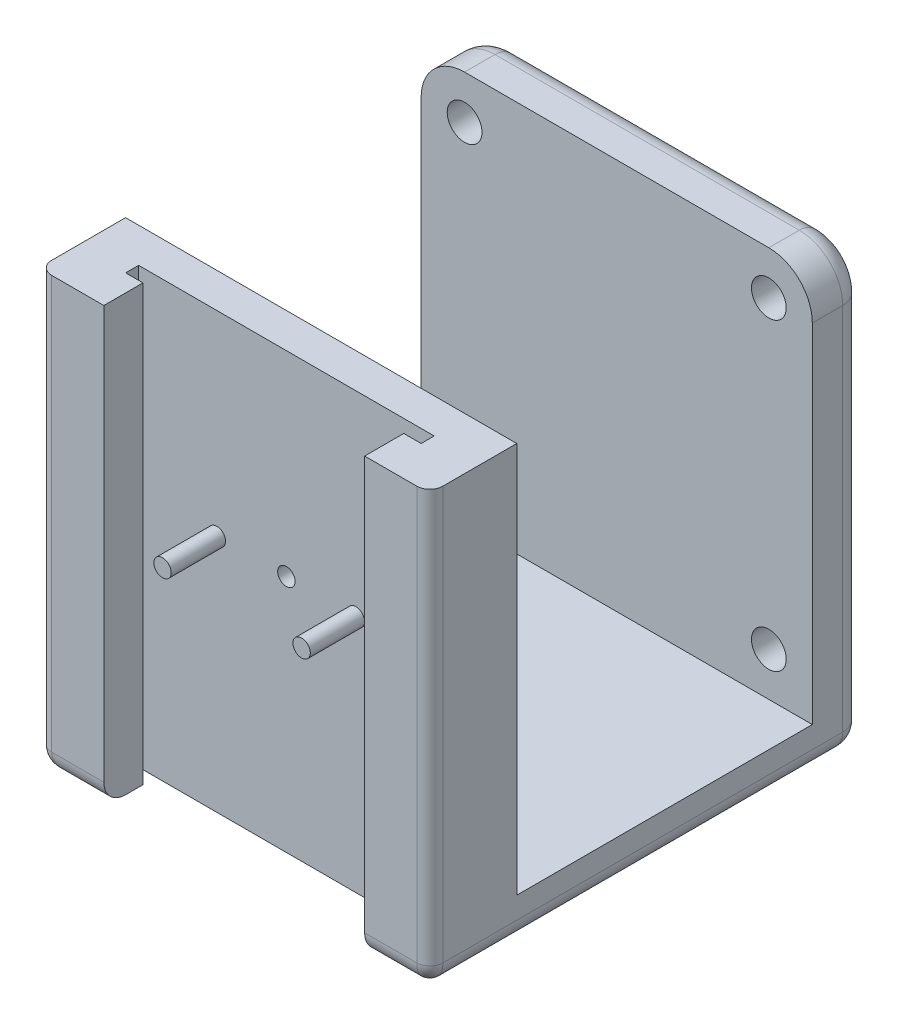
SolidWorks part; units mm, degrees
ref_plane "Front Plane" through (0, 0, 0) normal (0, 0, 1) x (1, 0, 0)
ref_plane "Top Plane" through (0, 0, 0) normal (0, 1, 0) x (1, 0, 0)
ref_plane "Right Plane" through (0, 0, 0) normal (1, 0, 0) x (0, 0, -1)
sketch "Sketch1" plane through (0, 0, 0) normal (0, 1, 0) x (1, 0, 0)
  line L0 (-79, 9) -> (-79, 12)
  line L1 (-90, 20) -> (0, 20)
  line L2 (-90, 20) -> (-90, 3)
  line L3 (-87, 0) -> (-3, 0)
  line L4 (0, 20) -> (0, 3)
  line L5 (-75, 0) -> (-15, 0)
  line L6 (-75, 0) -> (-75, 9)
  line L8 (-15, 0) -> (-15, 9)
  line L9 (-79, 9) -> (-75, 9)
  line L10 (-79, 12) -> (-11, 12)
  line L11 (-11, 9) -> (-11, 12)
  line L12 (-15, 9) -> (-11, 9)
  arc A0 (-3, 0) -> (0, 3) centre (-3, 3) ccw
  arc A1 (-90, 3) -> (-87, 0) centre (-87, 3) ccw
  point P15 (0, 0)
  dimension "D9" = 3
  dimension "D1" = 90
  dimension "D2" = 20
  dimension "D3" = 60
  dimension "D4" = 15
  dimension "D5" = 9
  dimension "D6" = 3
  dimension "D7" = 68
  dimension "D8" = 4
extrude "Boss-Extrude1" add sketch "Sketch1" along normal blind 100 contours L2 A1 L3 L6 L9 L0 L10 L11 L12 L8 A0 L4 L1 region at (-45, 0, -12.7601)
sketch "Sketch2" plane through (0, 0, -20) normal (0, 0, -1) x (-1, 0, 0)
  line L0 (90, 100) -> (90, 0) construction
  line L1 (0, 0) -> (90, 0)
  line L2 (0, 0) -> (0, 10)
  line L3 (0, 10) -> (90, 10)
  line L4 (90, 0) -> (90, 10)
  dimension "D1" = 10
extrude "Boss-Extrude3" add sketch "Sketch2" along normal blind 80
sketch "Sketch3" plane through (0, 10, 0) normal (0, 1, 0) x (1, 0, 0)
  line L0 (-90, 100) -> (-90, 20) construction
  line L1 (0, 100) -> (-90, 100)
  line L2 (0, 100) -> (0, 88)
  line L3 (0, 88) -> (-90, 88)
  line L4 (-90, 100) -> (-90, 88)
  dimension "D1" = 12
extrude "Boss-Extrude4" add sketch "Sketch3" along normal blind 90
sketch "Sketch4" plane through (0, 0, 0) normal (0, -1, 0) x (1, 0, 0)
  line L0 (0, -100) -> (0, -3) construction
  line L1 (0, -100) -> (-90, -100) construction
  circle A0 centre (-45, -55) radius 9
  dimension "D1" = 45
  dimension "D2" = 45
extrude "Boss-Extrude5" add sketch "Sketch4" along normal blind 25
sketch "Sketch5" plane through (0, 0, -100) normal (0, 0, -1) x (-1, 0, 0)
  line L2 (0, 100) -> (90, 100) construction
  line L3 (0, 100) -> (0, 0) construction
  circle A0 centre (10, 90) radius 4
  circle A1 centre (80, 90) radius 4
  circle A2 centre (80, 20) radius 4
  circle A3 centre (10, 20) radius 4
  dimension "D1" = 10
  dimension "D3" = 2
  dimension "D2" = 10
  dimension "D4" = 2
extrude "Cut-Extrude1" cut sketch "Sketch5" against normal blind 25
sketch "Sketch6" plane through (0, 0, -20) normal (0, 0, -1) x (-1, 0, 0)
  line L0 (0, 100) -> (0, 10) construction
  line L1 (90, 10) -> (0, 10) construction
  circle A0 centre (45, 55) radius 2
  circle A1 centre (54.9, 55) radius 2
  circle A2 centre (35.1, 55) radius 2
  dimension "D1" = 45
  dimension "D2" = 45
  dimension "D3" = 2
extrude "Cut-Extrude2" cut sketch "Sketch6" against normal blind 25 contours A0
sketch "Sketch7" plane through (0, 0, -12) normal (0, 0, 1) x (1, 0, 0)
  line L0 (-90, 10) -> (0, 10) construction
  line L1 (-15, 100) -> (-15, 0) construction
  circle A0 centre (-29, 55) radius 2
  circle A3 centre (-61, 55) radius 2
  dimension "D1" = 14
  dimension "D2" = 45
extrude "Boss-Extrude7" add sketch "Sketch7" along normal blind 12.5
fillet "Fillet1" radius 10 2 edges at (0, 100, -94) (-90, 100, -94)
fillet "Fillet2" radius 5 12 edges at (-9, 0, 0) (-0.8787, 0, -0.8787) (-81, 0, 0) (-89.1213, 0, -0.8787) (0, 45, -100) (-2.9289, 97.0711, -100) (-45, 100, -100) (-87.0711, 97.0711, -100) (0, 0, -51.5) (-90, 0, -51.5) (-45, 0, -100) (-90, 45, -100)
